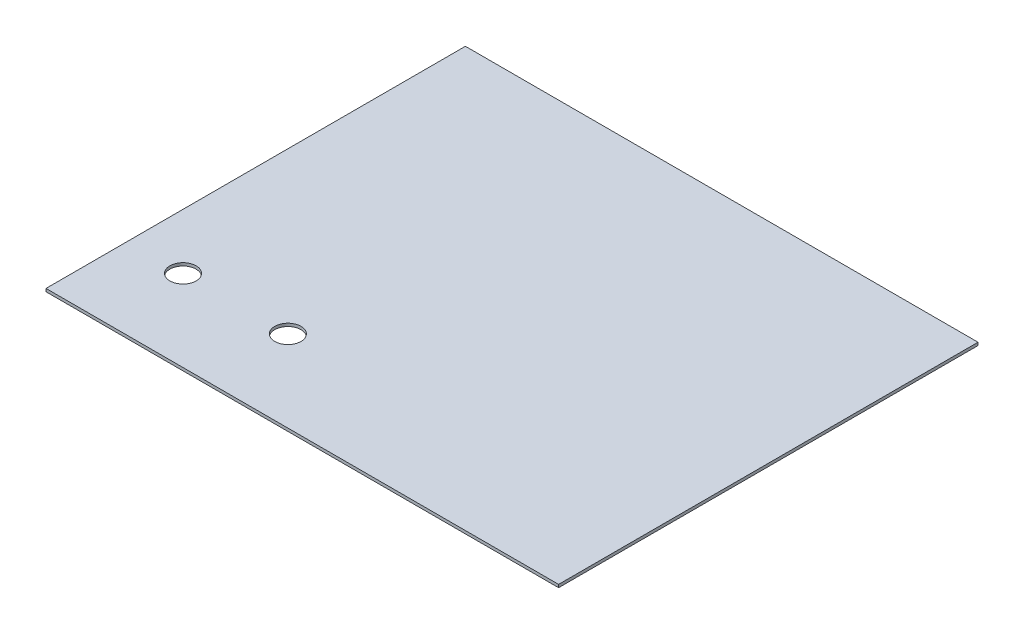
SolidWorks part; units mm, degrees
ref_plane "Front Plane" through (0, 0, 0) normal (0, 0, 1) x (1, 0, 0)
ref_plane "Top Plane" through (0, 0, 0) normal (0, 1, 0) x (1, 0, 0)
ref_plane "Right Plane" through (0, 0, 0) normal (1, 0, 0) x (0, 0, -1)
sketch "Sketch1" plane through (0, 0, 0) normal (0, 1, 0) x (1, 0, 0)
  line L1 (0, 0) -> (558.8, 0)
  line L2 (0, 0) -> (0, 457.2)
  line L3 (0, 457.2) -> (558.8, 457.2)
  line L4 (558.8, 0) -> (558.8, 457.2)
  dimension "D1" = 558.8
  dimension "D2" = 457.2
extrude "Boss-Extrude1" add sketch "Sketch1" along normal blind 3.175
sketch "Sketch2" plane through (0, 3.175, 0) normal (0, 1, 0) x (1, 0, 0)
  line L3 (60.4606, 88.9) -> (174.7606, 88.9) construction
  line L4 (0, 0) -> (558.8, 0) construction
  circle A2 centre (60.4606, 88.9) radius 14.2875
  circle A3 centre (174.7606, 88.9) radius 14.2875
  dimension "D3" = 28.575
  dimension "D4" = 28.575
  dimension "D5" = 114.3
  dimension "D8" = 88.9
extrude "Cut-Extrude1" cut sketch "Sketch2" against normal blind 3.175
